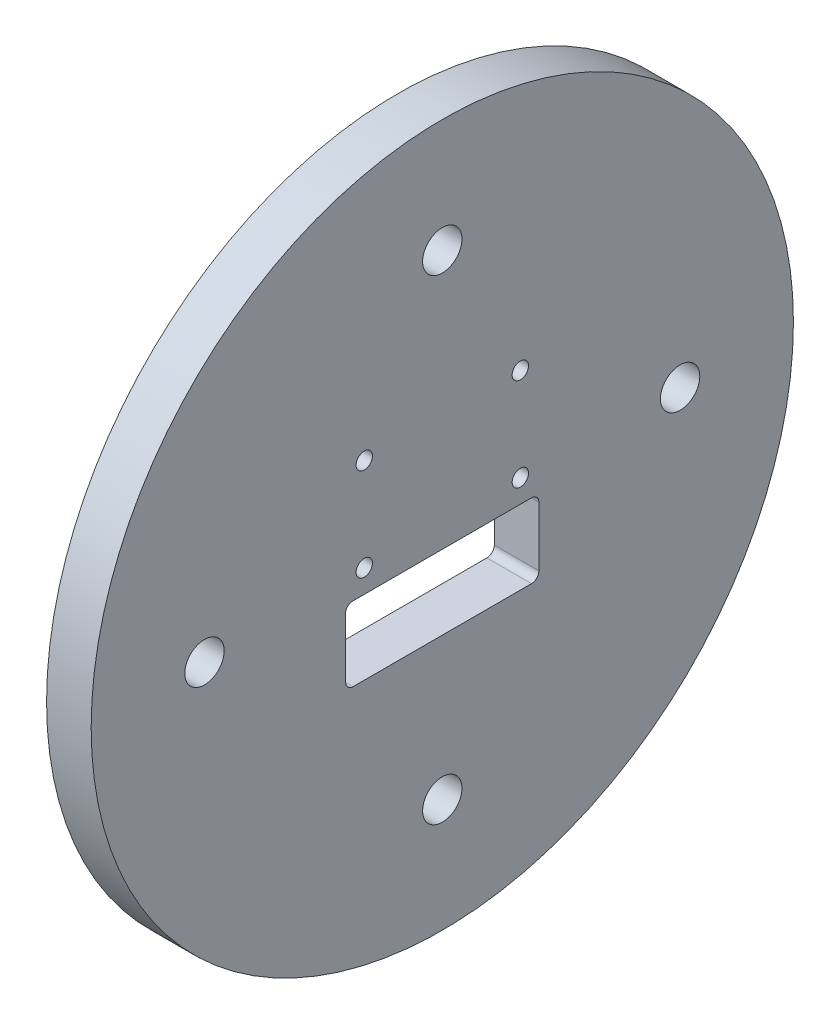
SolidWorks part; units mm, degrees
material "Perspex (TM) GS Acrylic Cast Sheet"
ref_plane "Front Plane" through (0, 0, 0) normal (0, 0, 1) x (1, 0, 0)
ref_plane "Top Plane" through (0, 0, 0) normal (0, 1, 0) x (1, 0, 0)
ref_plane "Right Plane" through (0, 0, 0) normal (1, 0, 0) x (0, 0, -1)
sketch "Sketch1" plane through (0, 0, 0) normal (1, 0, 0) x (0, 0, -1)
  circle A0 centre (0, 0) radius 47.25
  dimension "D2" = 94.5
extrude "Boss-Extrude1" add sketch "Sketch1" along normal blind 6
sketch "Sketch2" plane through (6, 0, 0) normal (1, 0, 0) x (0, 0, -1)
  line L0 (-12, -2.85) -> (12, -2.85)
  line L1 (13, -3.85) -> (13, -11.85)
  line L2 (12, -11.85) -> (-12, -11.85)
  line L3 (-13, -11.85) -> (-13, -4.1)
  line L4 (12, -12.85) -> (-12, -12.85)
  circle A0 centre (-10.5, 12.75) radius 1.1
  circle A1 centre (10.5, 12.75) radius 1.1
  circle A2 centre (10.5, 0.25) radius 1.1
  arc A3 (13, -3.85) -> (12, -2.85) centre (12, -3.85) ccw
  arc A4 (12, -11.85) -> (13, -10.85) centre (12, -10.85) ccw
  arc A5 (-13, -10.85) -> (-12, -11.85) centre (-12, -10.85) ccw
  arc A6 (-12, -2.85) -> (-13, -4.1) centre (-12.0319, -3.8495) ccw
  circle A7 centre (-10.5, 0.25) radius 1.1
  arc A8 (12, -12.85) -> (13, -11.85) centre (12, -11.85) ccw
  arc A9 (-12, -12.85) -> (-13, -11.85) centre (-12, -11.85) cw
  dimension "D2" = 1
  dimension "D3" = 2.85
  dimension "D4" = 10
extrude "Cut-Extrude1" cut sketch "Sketch2" against normal blind 20 contours L0 A6 L3 A5 L2 A4 L1 A3 | A9 L4 A8 L1 A4 L2 A5 L3 | A7 | A2 | A1 | A0 region at (6, -7.3494, 0.0021) region at (6, -12.3335, 0) region at (6, 0.25, -10.5) region at (6, 0.25, 10.5)
hole_wizard "M5 Clearance Hole1" positions "Sketch4" profile "Sketch3" hole size "M5" standard "ISO"
sketch "Sketch4" plane through (6, 0, 0) normal (1, 0, 0) x (0, 0, -1)
  point P0 (-32, 0)
  point P8 (0, 32)
  point P9 (32, 0)
  point P10 (0, -32)
  dimension "D1" = 32
  dimension "D2" = 4
sketch "Sketch3" plane through (6, 0, 32) normal (0, 1, 0) x (0, 0, -1)
  line L0 (0, 0) -> (0, 16.5923)
  line L1 (0, 16.5923) -> (2.65, 15)
  line L2 (2.65, 15) -> (2.65, 0)
  line L5 (2.65, 0) -> (0, 0)
  line L10 (0, 16.5923) -> (-2.65, 15) construction
  line L11 (0, -6.35) -> (0, 107.95) construction
  dimension "Hole Dia." = 5.3
  dimension "Hole Depth" = 15
  dimension "Drill Angle" = 118
ref_axis "Axis1" through (6, 0, 0) along (-1, 0, 0)
